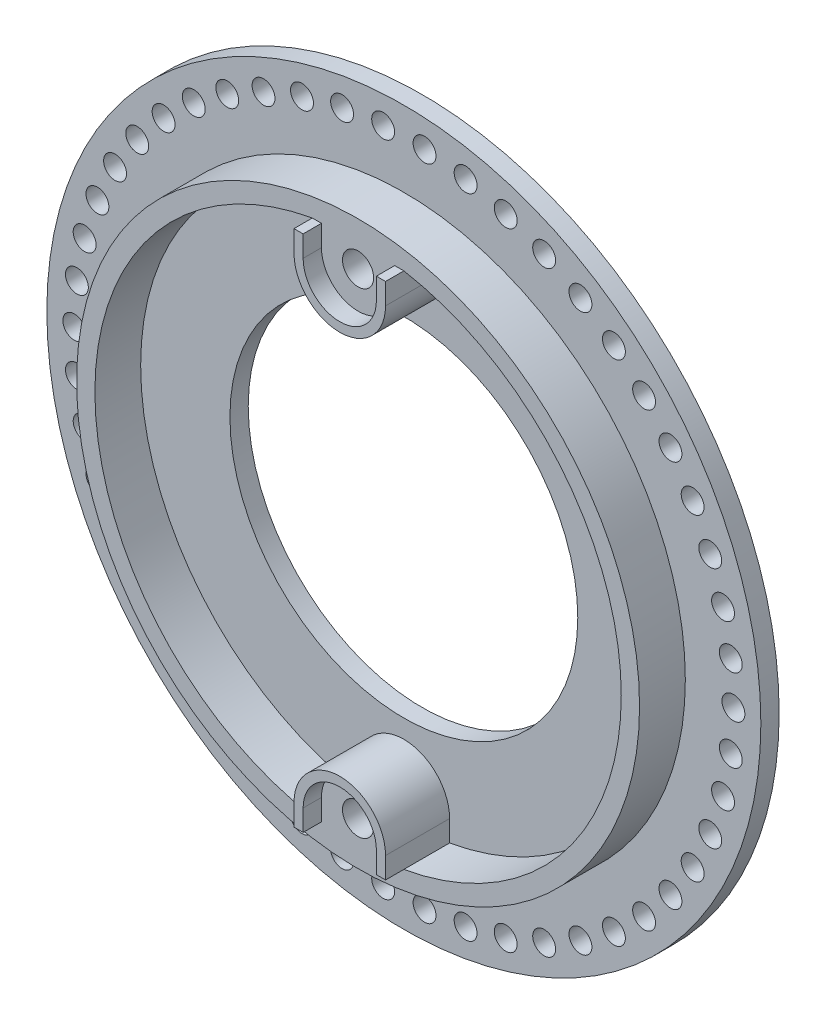
SolidWorks part; units mm, degrees
ref_plane "Front Plane" through (0, 0, 0) normal (0, 0, 1) x (1, 0, 0)
ref_plane "Top Plane" through (0, 0, 0) normal (0, 1, 0) x (1, 0, 0)
ref_plane "Right Plane" through (0, 0, 0) normal (1, 0, 0) x (0, 0, -1)
sketch "Sketch1" plane through (0, 0, 0) normal (0, 0, 1) x (1, 0, 0)
  circle A0 centre (0, 0) radius 39
  dimension "D1" = 78
extrude "Boss-Extrude1" add sketch "Sketch1" along normal blind 2
sketch "Sketch3" plane through (0, 0, 2) normal (0, 0, 1) x (1, 0, 0)
  line L0 (-5, 26) -> (-5, 28.3119)
  line L1 (5, 26) -> (5, 28.3119)
  line L2 (5, -26) -> (5, -28.3119)
  line L3 (-5, -26) -> (-5, -28.3119)
  circle A0 centre (0, 0) radius 30.75
  arc A1 (-5, 28.3119) -> (-5, -28.3119) centre (0, 0) ccw
  arc A2 (-5, 26) -> (5, 26) centre (0, 26) ccw
  circle A3 centre (0, 0) radius 28.75 construction
  arc A4 (5, -26) -> (-5, -26) centre (0, -26) ccw
  arc A5 (5, -28.3119) -> (5, 28.3119) centre (0, 0) ccw
  point P18 (0, 0)
  point P22 (-0.2453, 0)
  dimension "D1" = 61.5
  dimension "D3" = 10
  dimension "D5" = 2
  dimension "D4" = 26
  dimension "D2" = 2
extrude "Boss-Extrude2" add sketch "Sketch3" along normal blind 5 contours A1 L3 A4 L2 A5 L1 A2 L0 | A0
sketch "Sketch5" plane through (0, 0, 7) normal (0, 0, 1) x (1, 0, 0)
  circle A0 centre (0, -26) radius 1.7
  circle A1 centre (0, 26) radius 1.7
  point P7 (0, 0)
  dimension "D1" = 26
  dimension "D2" = 3.4
  dimension "D3" = 2
  dimension "D4" = 52
extrude "Cut-Extrude2" cut sketch "Sketch5" against normal up to surface (7 mm away) up to face at (39, 0, 0)
sketch "Sketch6" plane through (0, 0, 0) normal (0, 0, -1) x (-1, 0, 0)
  circle A0 centre (0, 26) radius 3
  circle A1 centre (0, -26) radius 3
  dimension "D1" = 6
  dimension "D2" = 6
  dimension "D3" = 26
  dimension "D4" = 26
extrude "Cut-Extrude3" cut sketch "Sketch6" against normal blind 4.5
sketch "Sketch7" plane through (0, 0, 0) normal (0, 0, -1) x (-1, 0, 0)
  circle A0 centre (0, 0) radius 19
  dimension "D1" = 38
extrude "Cut-Extrude4" cut sketch "Sketch7" against normal up to surface (2 mm away) up to face at (0, 0, 2)
sketch "Sketch8" plane through (0, 0, 2) normal (0, 0, 1) x (1, 0, 0)
  circle A0 centre (36, 0) radius 1.25
  circle A1 centre (35.7161, -4.512) radius 1.25
  circle A2 centre (34.869, -8.9528) radius 1.25
  circle A3 centre (33.472, -13.2525) radius 1.25
  circle A4 centre (31.547, -17.3431) radius 1.25
  circle A5 centre (29.1246, -21.1603) radius 1.25
  circle A6 centre (26.2429, -24.6437) radius 1.25
  circle A7 centre (22.9473, -27.7385) radius 1.25
  circle A8 centre (19.2898, -30.3958) radius 1.25
  circle A9 centre (15.3281, -32.5738) radius 1.25
  circle A10 centre (11.1246, -34.238) radius 1.25
  circle A11 centre (6.7457, -35.3623) radius 1.25
  circle A12 centre (2.2605, -35.929) radius 1.25
  circle A13 centre (-2.2605, -35.929) radius 1.25
  circle A14 centre (-6.7457, -35.3623) radius 1.25
  circle A15 centre (-11.1246, -34.238) radius 1.25
  circle A16 centre (-15.3281, -32.5738) radius 1.25
  circle A17 centre (-19.2898, -30.3958) radius 1.25
  circle A18 centre (-22.9473, -27.7385) radius 1.25
  circle A19 centre (-26.2429, -24.6437) radius 1.25
  circle A20 centre (-29.1246, -21.1603) radius 1.25
  circle A21 centre (-31.547, -17.3431) radius 1.25
  circle A22 centre (-33.472, -13.2525) radius 1.25
  circle A23 centre (-34.869, -8.9528) radius 1.25
  circle A24 centre (-35.7161, -4.512) radius 1.25
  circle A25 centre (-36, 0) radius 1.25
  circle A26 centre (-35.7161, 4.512) radius 1.25
  circle A27 centre (-34.869, 8.9528) radius 1.25
  circle A28 centre (-33.472, 13.2525) radius 1.25
  circle A29 centre (-31.547, 17.3431) radius 1.25
  circle A30 centre (-29.1246, 21.1603) radius 1.25
  circle A31 centre (-26.2429, 24.6437) radius 1.25
  circle A32 centre (-22.9473, 27.7385) radius 1.25
  circle A33 centre (-19.2898, 30.3958) radius 1.25
  circle A34 centre (-15.3281, 32.5738) radius 1.25
  circle A35 centre (-11.1246, 34.238) radius 1.25
  circle A36 centre (-6.7457, 35.3623) radius 1.25
  circle A37 centre (-2.2605, 35.929) radius 1.25
  circle A38 centre (2.2605, 35.929) radius 1.25
  circle A39 centre (6.7457, 35.3623) radius 1.25
  circle A40 centre (11.1246, 34.238) radius 1.25
  circle A41 centre (15.3281, 32.5738) radius 1.25
  circle A42 centre (19.2898, 30.3958) radius 1.25
  circle A43 centre (22.9473, 27.7385) radius 1.25
  circle A44 centre (26.2429, 24.6437) radius 1.25
  circle A45 centre (29.1246, 21.1603) radius 1.25
  circle A46 centre (31.547, 17.3431) radius 1.25
  circle A47 centre (33.472, 13.2525) radius 1.25
  circle A48 centre (34.869, 8.9528) radius 1.25
  circle A49 centre (35.7161, 4.512) radius 1.25
  point P104 (0, 0)
  dimension "D1" = 36
  dimension "D2" = 2.5
  dimension "D3" = 50
extrude "Cut-Extrude5" cut sketch "Sketch8" against normal up to surface (2 mm away) up to face at (-19, 0, 0)
fillet "Fillet1" radius 1.5 2 edges at (-3, -26, 4.5) (-3, 26, 4.5)
sketch "Sketch9" plane through (0, 0, 7) normal (0, 0, 1) x (1, 0, 0)
  line L2 (-4, 28.3119) -> (-5, 28.3119)
  line L3 (4, 28.3119) -> (5, 28.3119)
  line L4 (4, 28.3119) -> (4, 26)
  line L5 (-4, 26) -> (-4, 28.3119)
  line L6 (4, 28.3119) -> (4, 26)
  line L7 (-4, 26) -> (-4, 28.3119)
  line L8 (-5, 28.3119) -> (-5, 26)
  line L9 (5, 26) -> (5, 28.3119)
  line L10 (-5, -26) -> (-5, -28.3119)
  line L11 (-4, -28.3119) -> (-5, -28.3119)
  line L12 (-4, -28.3119) -> (-4, -26)
  line L13 (4, -26) -> (4, -28.3119)
  line L14 (4, -28.3119) -> (5, -28.3119)
  line L15 (5, -28.3119) -> (5, -26)
  arc A2 (4, -26) -> (-4, -26) centre (0, -26) ccw
  arc A4 (-5, 26) -> (5, 26) centre (0, 26) ccw
  arc A5 (-4, 26) -> (4, 26) centre (0, 26) ccw
  arc A6 (-4, 26) -> (4, 26) centre (0, 26) ccw
  arc A8 (5, -26) -> (-5, -26) centre (0, -26) ccw
  point P26 (0, 0)
  dimension "D1" = 2
  dimension "D2" = 1
extrude "Boss-Extrude3" add sketch "Sketch9" along normal blind 2
equation "\"D2@Sketch6\"=\"D1@Sketch6\""
